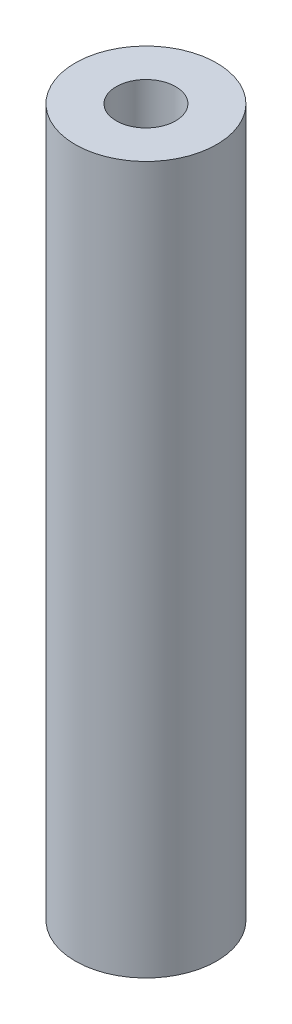
SolidWorks part; units mm, degrees
material "ABS"
ref_plane "Front Plane" through (0, 0, 0) normal (0, 0, 1) x (1, 0, 0)
ref_plane "Top Plane" through (0, 0, 0) normal (0, 1, 0) x (1, 0, 0)
ref_plane "Right Plane" through (0, 0, 0) normal (1, 0, 0) x (0, 0, -1)
sketch "Sketch1" plane through (0, 0, 0) normal (0, 1, 0) x (1, 0, 0)
  circle A0 centre (0, 0) radius 6.35
  circle A1 centre (0, 0) radius 2.667
  dimension "D1" = 12.7
  dimension "D2" = 5.334
extrude "Boss-Extrude1" add sketch "Sketch1" along normal blind 63.5
sketch "Sketch2" plane through (0, 0, 0) normal (0, -1, 0) x (-1, 0, 0)
  circle A0 centre (0, 0) radius 9.525
  circle A1 centre (0, 0) radius 2.54
  dimension "D1" = 19.05
extrude "Boss-Extrude2" [suppressed] add sketch "Sketch2" against normal blind 7.62
chamfer "Chamfer1" [suppressed] distance 3.175 angle 68
fillet "Fillet1" [suppressed] radius 12.7
sketch "Sketch3" plane through (0, 63.5, 0) normal (0, 1, 0) x (1, 0, 0)
  circle A0 centre (0, 0) radius 9.525
  circle A1 centre (0, 0) radius 2.54
  dimension "D1" = 19.05
extrude "Boss-Extrude3" [suppressed] add sketch "Sketch3" against normal blind 7.62
chamfer "Chamfer2" [suppressed] distance 3.175 angle 68
fillet "Fillet2" [suppressed] radius 12.7
sketch "Sketch4" plane through (0, 0, 0) normal (0, 0, 1) x (1, 0, 0)
  line L1 (-14.5993, 37.9681) -> (14.5993, 37.9681)
  line L2 (-14.5993, 37.9681) -> (-14.5993, -4.7123)
  line L3 (-14.5993, -4.7123) -> (14.5993, -4.7123)
  line L4 (14.5993, 37.9681) -> (14.5993, -4.7123)
  line L5 (-14.5993, 37.9681) -> (14.5993, -4.7123) construction
  line L6 (-14.5993, -4.7123) -> (14.5993, 37.9681) construction
  point P0 (0, 16.6279)
extrude "Cut-Extrude1" [suppressed] cut sketch "Sketch4" along normal through all from offset 6.35
